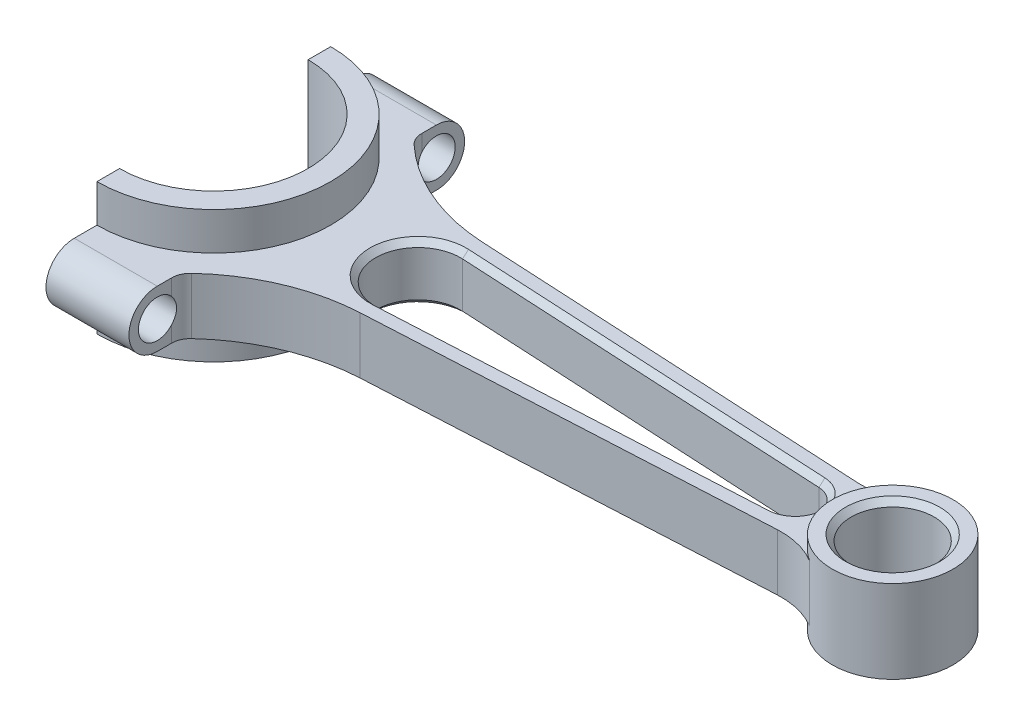
SolidWorks part; units mm, degrees
ref_plane "Front Plane" through (0, 0, 0) normal (0, 0, 1) x (1, 0, 0)
ref_plane "Top Plane" through (0, 0, 0) normal (0, 1, 0) x (1, 0, 0)
ref_plane "Right Plane" through (0, 0, 0) normal (1, 0, 0) x (0, 0, -1)
sketch "Sketch1" plane through (0, 0, 0) normal (0, 1, 0) x (1, 0, 0)
  line L0 (0, 0) -> (-26926.9819, 0) construction
  line L1 (0, 0) -> (0, -26926.9819) construction
  line L2 (0, 25) -> (0, 44.5)
  line L3 (0, 44.5) -> (22, 44.5)
  line L4 (22, 44.5) -> (22, 33.1639)
  line L5 (22, -44.5) -> (22, -33.1639)
  line L6 (0, -44.5) -> (22, -44.5)
  line L7 (0, -25) -> (0, -44.5)
  line L8 (154.4644, 5.9918) -> (54.7383, 11.2182)
  line L9 (154.4644, -5.9918) -> (54.7383, -11.2182)
  line L10 (154.7261, 10.9849) -> (55, 16.2113)
  line L11 (154.7261, -10.9849) -> (55, -16.2113)
  line L12 (55, 16.2113) -> (55, 66.7421) construction
  line L13 (55, 16.2113) -> (57.6168, 66.1428) construction
  line L14 (154.7261, 10.9849) -> (160.1111, 10.7027)
  line L15 (154.7261, -10.9849) -> (160.1111, -10.7027)
  arc A0 (0, -31) -> (0, 31) centre (0, 0) ccw
  arc A1 (0, -25) -> (0, 25) centre (0, 0) ccw
  circle A2 centre (180, 0) radius 16
  circle A3 centre (180, 0) radius 11
  arc A4 (54.7383, 11.2182) -> (54.7383, -11.2182) centre (54.1504, 0) ccw
  arc A5 (154.4644, -5.9918) -> (154.4644, 5.9918) centre (154.1504, 0) ccw
  arc A8 (23.5981, 29.4995) -> (55, 16.2113) centre (57.6168, 66.1428) ccw
  arc A9 (55, 16.2113) -> (55, -16.2113) centre (54.1504, 0) ccw construction
  arc A10 (23.5981, -29.4995) -> (55, -16.2113) centre (57.6168, -66.1428) cw
  arc A11 (22, -33.1639) -> (23.5981, -29.4995) centre (27, -33.1639) cw
  arc A12 (22, 33.1639) -> (23.5981, 29.4995) centre (27, 33.1639) ccw
  arc A13 (154.7261, -10.9849) -> (154.7261, 10.9849) centre (154.1504, 0) ccw construction
  arc A14 (160.1111, 10.7027) -> (171.6257, 13.6335) centre (161.1579, 30.6753) ccw
  arc A15 (160.1111, -10.7027) -> (171.6257, -13.6335) centre (161.1579, -30.6753) cw
  point P37 (22, -31.0509)
  point P40 (22, 31.0509)
  point P42 (41.3289, 8.1262)
  dimension "D1" = 50
  dimension "D2" = 62
  dimension "D5" = 32
  dimension "D6" = 22
  dimension "D9" = 100
  dimension "D10" = 12
  dimension "D14" = 100
  dimension "D15" = 5
  dimension "D16" = 20
  dimension "D3" = 89
  dimension "D4" = 22
  dimension "D7" = 180
  dimension "D8" = 125
  dimension "D11" = 3
  dimension "D12" = 5
  dimension "D13" = 3
extrude "Boss-Extrude1" add sketch "Sketch1" along normal mid plane 22 contours A2 A3 region at (187.5897, 0, -13.5691)
extrude "Boss-Extrude2" add sketch "Sketch1<3>" along normal mid plane 35 separate body contours A1 L7 A0 L2 region at (0.6932, 0, -28)
sketch "Sketch1<3>" plane through (0, 0, 0) normal (0, 1, 0) x (1, 0, 0) same geometry as "Sketch1"
extrude "Boss-Extrude3" add sketch "Sketch1<4>" along normal mid plane 15 contours L15 A15 A2 A14 L14 L10 A8 A12 L4 L3 L2 A0 L7 L6 L5 A11 A10 L11 A5 L9 A4 L8 region at (1.9333, 0, -37.75)
sketch "Sketch1<4>" plane through (0, 0, 0) normal (0, 1, 0) x (1, 0, 0) same geometry as "Sketch1"
chamfer "Chamfer1" distance 1.5 angle 45 10 edges at (180, -11, 11) (104.6014, -7.5, -8.605) (160.1504, -7.5, 0) (42.9168, -7.5, 0) (104.6014, -7.5, 8.605) (180, 11, 11) (160.1504, 7.5, 0) (104.6014, 7.5, -8.605) (104.6014, 7.5, 8.605) (42.9168, 7.5, 0)
fillet "Fillet1" 2 edges at (11, 7.5, 44.5) (11, -7.5, 44.5) type full round first side face at (103.1067, 7.5, 0) second side face at (103.1067, -7.5, 0) middle face at (11, 0, 44.5)
fillet "Fillet2" 2 edges at (11, 7.5, -44.5) (11, -7.5, -44.5) type full round first side face at (103.1067, 7.5, 0) second side face at (103.1067, -7.5, 0) middle face at (11, 0, -44.5)
sketch "Sketch2" plane through (0, 0, 0) normal (-1, 0, 0) x (0, 0, 1)
  circle A0 centre (-37, 0) radius 5
  circle A1 centre (37, 0) radius 5
  dimension "D1" = 10
extrude "Cut-Extrude1" cut sketch "Sketch2" against normal through all
